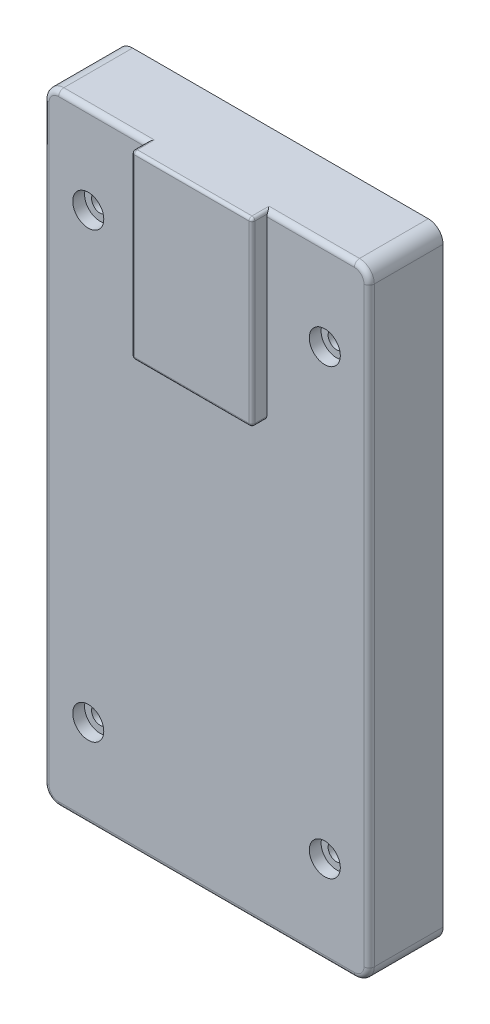
SolidWorks part; units mm, degrees
ref_plane "Front Plane" through (0, 0, 0) normal (0, 0, 1) x (1, 0, 0)
ref_plane "Top Plane" through (0, 0, 0) normal (0, 1, 0) x (1, 0, 0)
ref_plane "Right Plane" through (0, 0, 0) normal (1, 0, 0) x (0, 0, -1)
sketch "Sketch1" plane through (0, 0, 0) normal (0, 0, 1) x (1, 0, 0)
  line L1 (-22, -42) -> (22, -42)
  line L2 (-22, -42) -> (-22, 42)
  line L3 (-22, 42) -> (22, 42)
  line L4 (22, -42) -> (22, 42)
  line L5 (-22, -42) -> (22, 42) construction
  line L6 (-22, 42) -> (22, -42) construction
  point P0 (0, 0)
  dimension "D1" = 84
  dimension "D2" = 44
extrude "Boss-Extrude1" add sketch "Sketch1" along normal blind 10
sketch "Sketch2" plane through (0, 0, 10) normal (0, 0, 1) x (1, 0, 0)
  line L0 (-22, 42) -> (-8.15, 42) construction
  line L1 (22, 42) -> (-22, 42) construction
  line L3 (-8.15, 42) -> (8.15, 42)
  line L4 (-8.15, 42) -> (-8.15, 17.5)
  line L5 (-8.15, 17.5) -> (8.15, 17.5)
  line L6 (8.15, 42) -> (8.15, 17.5)
  dimension "D1" = 13.85
  dimension "D2" = 24.5
  dimension "D3" = 16.3
extrude "Boss-Extrude2" add sketch "Sketch2" along normal blind 2 contours L4 L5 L6 L3
hole_wizard "CBORE for M2 Pan Head Machine Screw1" positions "Sketch5" profile "Sketch4" counterbore size "M2" standard "ANSI Metric" end condition through all
sketch "Sketch5" plane through (0, 0, 10) normal (0, 0, 1) x (1, 0, 0)
  point P0 (16, 30)
  point P3 (-16, 30)
  point P6 (-16, -30)
  point P9 (16, -30)
sketch "Sketch4" plane through (16, 30, 10) normal (1, 0, 0) x (0, -1, 0)
  line L0 (0, 0) -> (0, 10)
  line L1 (0, 10) -> (1.15, 10)
  line L3 (1.15, 10) -> (1.15, 1.6)
  line L4 (1.15, 1.6) -> (2.1, 1.6)
  line L5 (2.1, 1.6) -> (2.1, 0)
  line L7 (2.1, 0) -> (0, 0)
  line L11 (0, -6.35) -> (0, 107.95) construction
  dimension "Thru Hole Dia." = 2.3
  dimension "Thru Hole Depth" = 10
  dimension "C'Bore Dia." = 4.2
  dimension "C'Bore Depth" = 1.6
fillet "Fillet2" radius 2 1 edges at (22, -42, 5)
fillet "Fillet3" radius 2 1 edges at (-22, -42, 5)
fillet "Fillet4" radius 2 1 edges at (-22, 42, 5)
fillet "Fillet5" radius 2 1 edges at (22, 42, 5)
fillet "Fillet6" radius 0.4 4 edges at (8.15, 29.75, 12) (0, 17.5, 12) (-8.15, 29.75, 12) (0, 42, 12)
fillet "Fillet7" radius 0.4 4 edges at (8.0328, 17.6172, 11.8828) (8.0328, 41.8828, 11.8828) (8.15, 17.5, 10.8)
fillet "Fillet8" radius 0.4 4 edges at (-8.0328, 17.6172, 11.8828) (-8.0328, 41.8828, 11.8828) (-8.15, 17.5, 10.8)
fillet "Fillet9" radius 0.7 9 edges at (21.4142, 41.4142, 10) (-21.4142, 41.4142, 10) (21.4142, -41.4142, 10) (-21.4142, -41.4142, 10) (0, -42, 10) (22, 0, 10) (-22, 0, 10)
